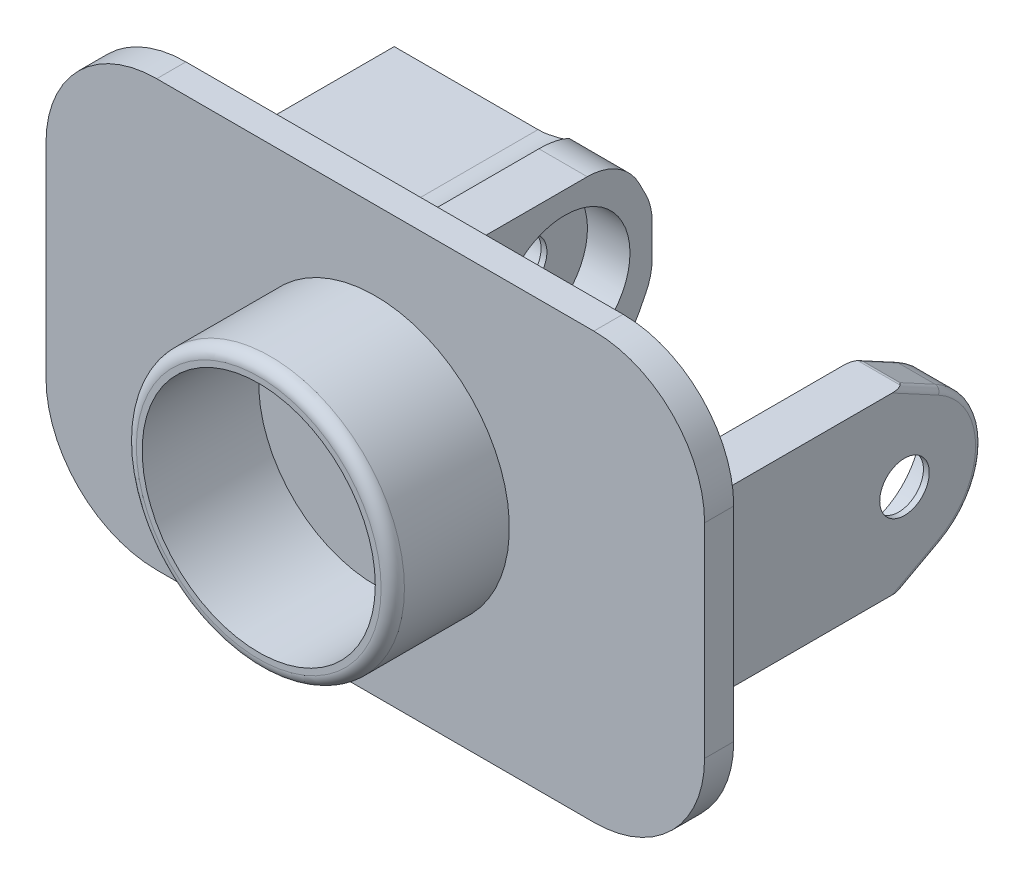
SolidWorks part; units mm, degrees
ref_plane "Alzado" through (0, 0, 0) normal (1, 0, 0) x (0, 1, 0)
ref_plane "Planta" through (0, 0, 0) normal (0, 0, 1) x (0, 1, 0)
ref_plane "Vista lateral" through (0, 0, 0) normal (0, 1, 0) x (-1, 0, 0)
sketch "Croquis2" plane through (0, 0, 0) normal (0, 0, 1) x (0, 1, 0)
  line L0 (0, 0) -> (0, 75) construction
  line L1 (-37.5, -40) -> (37.5, -40)
  line L2 (-37.5, -40) -> (-37.5, 75)
  line L3 (-37.5, 75) -> (37.5, 75)
  line L4 (37.5, -40) -> (37.5, 75)
  point P0 (0, 0)
  dimension "D1" = 115
  dimension "D2" = 75
  dimension "D3" = 40
extrude "Saliente-Extruir1" add sketch "Croquis2" along normal blind 5
sketch "Croquis3" plane through (0, 0, 0) normal (0, 0, -1) x (1, 0, 0)
  line L0 (0, -55) -> (0, 55) construction
  line L1 (25, 15) -> (33.3, 15)
  line L2 (25, 15) -> (25, -15)
  line L3 (25, -15) -> (33.3, -15)
  line L4 (33.3, 15) -> (33.3, -15)
  line L5 (-33.3, 15) -> (-33.3, -15)
  line L6 (-25, -15) -> (-33.3, -15)
  line L7 (-25, 15) -> (-25, -15)
  line L8 (-25, 15) -> (-33.3, 15)
  point P4 (25, 0)
  point P12 (-25, 0)
  dimension "D1" = 30
  dimension "D2" = 8.3
  dimension "D3" = 25
  dimension "D4" = 15
extrude "Saliente-Extruir2" add sketch "Croquis3" along normal blind 35 contours L4 L1 L2 L3 region at (29.15, 0, 0)
sketch "Croquis4" plane through (25, 0, 0) normal (-1, 0, 0) x (0, -1, 0)
  line L1 (15, -35) -> (11.616, -41.2697)
  line L2 (-11.616, -41.2697) -> (-15, -35)
  line L3 (-15, -35) -> (15, -35)
  circle A0 centre (0, -35) radius 11.2
  circle A1 centre (0, -35) radius 13.2
  dimension "D1" = 22.4
  dimension "D2" = 2
extrude "Saliente-Extruir4" add sketch "Croquis4" against normal up to surface (8.3 mm away) contours A0 L2 | A0 L1 | A1 L2 region at (25, -13.5873, -36.6068) region at (25, 0, -47.9048) region at (25, 13.5873, -36.6068) up to face at (33.3, 0, -17.5)
fillet "Redondeo4" radius 1 8 edges at (25, -13.308, -38.1348) (25, 0, -48.2) (33.3, -13.308, -38.1348) (33.3, 0, -48.2) (25, 13.308, -38.1348) (33.3, 13.308, -38.1348) (29.15, 15, -35) (29.15, -15, -35)
extrude "Cortar-Extruir1" cut sketch "Croquis4<6>" against normal through all contours L3 A0 region at (25, 0, -30.2466)
sketch "Croquis4<6>" plane through (25, 0, 0) normal (-1, 0, 0) x (0, -1, 0) same geometry as "Croquis4"
extrude "Saliente-Extruir6" add sketch "Croquis3<3>" along normal blind 50 contours L7 L8 L5 L6 region at (-29.15, 0, 0)
sketch "Croquis3<3>" plane through (0, 0, 0) normal (0, 0, -1) x (1, 0, 0) same geometry as "Croquis3"
sketch "Croquis8" plane through (-33.3, 0, 0) normal (-1, 0, 0) x (0, -1, 0)
  circle A0 centre (0, -35) radius 11.2 construction
  circle A1 centre (0, -35) radius 11.2
extrude "Cortar-Extruir2" cut sketch "Croquis8" against normal through all
sketch "Croquis14" plane through (33.3, 0, 0) normal (1, 0, 0) x (0, 1, 0)
  circle A0 centre (0, -35) radius 11.2 construction
  circle A1 centre (0, -35) radius 11.2
  circle A2 centre (0, -35) radius 4.25
  dimension "D1" = 8.5
extrude "Saliente-Extruir9" add sketch "Croquis14" against normal blind 1
sketch "Croquis15" plane through (-33.3, 0, 0) normal (-1, 0, 0) x (0, -1, 0)
  circle A0 centre (0, -35) radius 11.2 construction
  circle A1 centre (0, -35) radius 11.2
  circle A2 centre (0, -35) radius 4.25
  dimension "D1" = 8.5
extrude "Saliente-Extruir10" add sketch "Croquis15" against normal blind 1
sketch "Croquis9" plane through (-33.3, 0, 0) normal (-1, 0, 0) x (0, -1, 0)
  line L0 (15, -50) -> (-15, -50) construction
  line L1 (-6.6, -46.05) -> (6.6, -46.05)
  line L2 (-6.6, -46.05) -> (-6.6, -13.05)
  line L3 (-6.6, -13.05) -> (6.6, -13.05)
  line L4 (6.6, -46.05) -> (6.6, -13.05)
  line L5 (-6.6, -46.05) -> (6.6, -13.05) construction
  line L6 (-6.6, -13.05) -> (6.6, -46.05) construction
  line L7 (-8.6, -48.05) -> (-8.6, -11.05)
  line L8 (-8.6, -11.05) -> (8.6, -11.05)
  line L9 (8.6, -48.05) -> (8.6, -11.05)
  line L10 (-8.6, -48.05) -> (8.6, -48.05)
  line L12 (6.6, -46.05) -> (6.6, -13.05) construction
  line L14 (-6.6, -46.05) -> (-6.6, -13.05) construction
  circle A2 centre (0, -35) radius 5 construction
  arc A4 (2.9, -29.4635) -> (-2.9, -29.4635) centre (0, -29.7657) ccw
  arc A6 (-2.9, -29.4635) -> (2.9, -29.4635) centre (0, -35) ccw
  point P8 (0, -29.55)
  point P17 (0, -41.25)
  point P19 (0, -26.85)
  point P21 (0, -40)
  dimension "D5" = 10
  dimension "D6" = 5.8
  dimension "D9" = 6.25
  dimension "D1" = 33
  dimension "D2" = 13.2
  dimension "D3" = 11.05
  dimension "D7" = 14.4
  dimension "D8" = 15
  dimension "D4" = 2
extrude "Saliente-Extruir11" add sketch "Croquis9" along normal blind 34 contours L7 L10 L9 L8 L4 L1 L2 L3 region at (-33.3, 8.192, -29.55)
extrude "Saliente-Extruir12" add sketch "Croquis9<5>" along normal blind 7.5 contours L1 L4 L3 L2 A6 A4 region at (-33.3, 6.2446, -29.55)
sketch "Croquis9<5>" plane through (-33.3, 0, 0) normal (-1, 0, 0) x (0, -1, 0) same geometry as "Croquis9"
sketch "Croquis16" plane through (-40.8, 0, 0) normal (-1, 0, 0) x (0, -1, 0)
  line L0 (6.6, -46.05) -> (6.6, -13.05) construction
  line L1 (-6.6, -13.05) -> (6.6, -13.05)
  line L2 (-6.6, -13.05) -> (-6.6, -17.9)
  line L3 (-6.6, -17.9) -> (6.6, -17.9)
  line L4 (6.6, -13.05) -> (6.6, -17.9)
  line L5 (-6.6, -46.05) -> (-6.6, -13.05) construction
  line L6 (6.6, -46.05) -> (-6.6, -46.05)
  line L7 (6.6, -46.05) -> (6.6, -41.2)
  line L8 (6.6, -41.2) -> (0.789, -41.2)
  line L9 (-6.6, -46.05) -> (-6.6, -41.2)
  line L10 (-0.789, -41.2) -> (-6.6, -41.2)
  arc A0 (-2.9, -29.4635) -> (2.9, -29.4635) centre (0, -35) ccw construction
  arc A1 (-0.789, -41.2) -> (0.789, -41.2) centre (0, -35) ccw
  circle A2 centre (0, -15.9) radius 0.85
  circle A3 centre (0, -43.2) radius 0.85
  arc M9 (2.9, -29.4635) -> (-2.9, -29.4635) centre (0, -35) cw
  line M11 (-6.6, -46.05) -> (6.6, -46.05)
  line M12 (6.6, -46.05) -> (6.6, -13.05)
  line M13 (6.6, -13.05) -> (-6.6, -13.05)
  line M14 (-6.6, -13.05) -> (-6.6, -46.05)
  dimension "D2" = 1.7
  dimension "D3" = 2.85
  dimension "D4" = 2.85
  dimension "D1" = 23.3
extrude "Saliente-Extruir13" add sketch "Croquis16" along normal blind 1.7 contours A2 | L3 A2 M14 M12 M13 | L10 L8 A3 M9 M14 M11 M12 | A3 region at (-40.8, 0, -13.1906) region at (-40.8, 3.6945, -41.3406) region at (-40.8, 0, -15.9) region at (-40.8, 0, -43.2)
extrude "Saliente-Extruir14" add sketch "Croquis16<3>" along normal blind 6 contours A2 | A3 region at (-40.8, 0, -15.9) region at (-40.8, 0, -43.2)
sketch "Croquis16<3>" plane through (-40.8, 0, 0) normal (-1, 0, 0) x (0, -1, 0) same geometry as "Croquis16"
fillet "Redondeo5" radius 0.5 4 edges at (-42.5, -0.85, -43.2) (-42.5, -0.85, -15.9) (-46.8, -0.85, -43.2) (-46.8, -0.85, -15.9)
sketch "Croquis17" plane through (0, 0, -48.05) normal (0, 0, -1) x (1, 0, 0)
  line L0 (-67.3, -8.6) -> (-67.3, 8.6) construction
  line L1 (-67.3, -8.6) -> (-67.3, 8.6)
  line L2 (-67.3, 8.6) -> (-62.3, 8.6)
  line L3 (-67.3, 8.6) -> (-33.3, 8.6) construction
  line L4 (-62.3, 8.6) -> (-62.3, 3.5)
  line L5 (-62.3, 3.5) -> (-57.3, 3.5)
  line L6 (-57.3, 3.5) -> (-57.3, -3.5)
  line L7 (-57.3, -3.5) -> (-62.3, -3.5)
  line L8 (-62.3, -3.5) -> (-62.3, -8.6)
  line L9 (-62.3, -8.6) -> (-67.3, -8.6)
  line L10 (-65.3, 7.6) -> (-65.3, 6.6)
  line L11 (-65.3, 7.6) -> (-62.3, 7.6)
  line L12 (-65.3, -6.6) -> (-67.3, -6.6)
  line L13 (-65.3, -7.6) -> (-65.3, -6.6)
  line L14 (-57.3, 0) -> (-67.3, 0) construction
  line L15 (-65.3, 6.6) -> (-67.3, 6.6)
  line L16 (-65.3, -7.6) -> (-62.3, -7.6)
  line L17 (-65.3, 6.6) -> (-62.3, 6.6)
  line L18 (-65.3, -6.6) -> (-62.3, -6.6)
  line M14 (-67.3, 8.6) -> (-67.3, -8.6)
  line M15 (-67.3, -8.6) -> (-33.3, -8.6)
  dimension "D1" = 7
  dimension "D2" = 10
  dimension "D3" = 5
  dimension "D4" = 2
  dimension "D5" = 3
  dimension "D6" = 1
extrude "Cortar-Extruir3" cut sketch "Croquis17" against normal up to surface (2 mm away) contours L6 L14 L1 L8 L7 M15 | L14 L6 L5 L4 L11 L2 M14 region at (-63.0673, 0, -48.05) up to face at (-54.9, 0, -46.05)
extrude "Cortar-Extruir4" cut sketch "Croquis17<4>" against normal up to surface (35 mm away) contours L10 L17 L4 L11 | L18 L13 L16 L8 region at (-63.8, 7.1, -48.05) region at (-63.8, -7.1, -48.05) up to face at (-54.9, 0, -13.05)
sketch "Croquis17<4>" plane through (0, 0, -48.05) normal (0, 0, -1) x (1, 0, 0) same geometry as "Croquis17"
fillet "Redondeo6" radius 10 3 edges at (-33.3, -8.6, -29.55) (-33.3, 8.6, -29.55) (-33.3, 0, -48.05)
chamfer "Chaflán1" distance 20 angle 45 1 edges at (-33.3, 0, -11.05)
chamfer "Chaflán2" distance 5 angle 63 1 edges at (-29.15, -15, -50) first distance on face at (-29.15, -15, -25)
chamfer "Chaflán3" distance 5 angle 63 1 edges at (-29.15, 15, -50) first distance on face at (-29.15, 15, -25)
fillet "Redondeo7" radius 10 2 edges at (-29.15, 5.1869, -50) (-29.15, -5.1869, -50)
fillet "Redondeo8" radius 10 2 edges at (-29.15, 15, -45) (-29.15, -15, -45)
fillet "Redondeo9" radius 20 4 edges at (-75, 37.5, 2.5) (40, 37.5, 2.5) (40, -37.5, 2.5) (-75, -37.5, 2.5)
sketch "Sketch3" plane through (0, 0, 5) normal (0, 0, 1) x (1, 0, 0)
  circle A0 centre (-17.5, 0) radius 23
  circle A1 centre (-17.5, 0) radius 20
  dimension "D1" = 40
  dimension "D2" = 3
extrude "Boss-Extrude1" add sketch "Sketch3" along normal blind 20
sketch "Sketch5" plane through (0, 0, 5) normal (0, 0, 1) x (1, 0, 0)
  line L0 (40, -17.5) -> (40, 17.5) construction
  line L1 (-55, -37.5) -> (20, -37.5) construction
  line L2 (-75, 17.5) -> (-75, -17.5) construction
  line L3 (20, 37.5) -> (-55, 37.5) construction
  line L4 (40, -17.5) -> (40, 17.5)
  line L5 (-55, -37.5) -> (20, -37.5)
  line L6 (-75, 17.5) -> (-75, -17.5)
  line L7 (20, 37.5) -> (-55, 37.5)
  line L8 (20, 36.5) -> (-55, 36.5)
  line L9 (-74, 17.5) -> (-74, -17.5)
  line L10 (-55, -36.5) -> (20, -36.5)
  line L11 (39, -17.5) -> (39, 17.5)
  arc A0 (40, 17.5) -> (20, 37.5) centre (20, 17.5) ccw construction
  arc A1 (20, -37.5) -> (40, -17.5) centre (20, -17.5) ccw construction
  arc A2 (-75, -17.5) -> (-55, -37.5) centre (-55, -17.5) ccw construction
  arc A3 (-55, 37.5) -> (-75, 17.5) centre (-55, 17.5) ccw construction
  arc A4 (40, 17.5) -> (20, 37.5) centre (20, 17.5) ccw
  arc A5 (20, -37.5) -> (40, -17.5) centre (20, -17.5) ccw
  arc A6 (-75, -17.5) -> (-55, -37.5) centre (-55, -17.5) ccw
  arc A7 (-55, 37.5) -> (-75, 17.5) centre (-55, 17.5) ccw
  arc A8 (-55, 36.5) -> (-74, 17.5) centre (-55, 17.5) ccw
  arc A9 (-74, -17.5) -> (-55, -36.5) centre (-55, -17.5) ccw
  arc A10 (20, -36.5) -> (39, -17.5) centre (20, -17.5) ccw
  arc A11 (39, 17.5) -> (20, 36.5) centre (20, 17.5) ccw
  dimension "D1" = 1
extrude "Cut-Extrude1" cut sketch "Sketch5" against normal blind 20
fillet "Fillet1" radius 2 1 edges at (5.5, 0, 25)
equation "\"D4@Croquis16\"=\"D3@Croquis16\""
